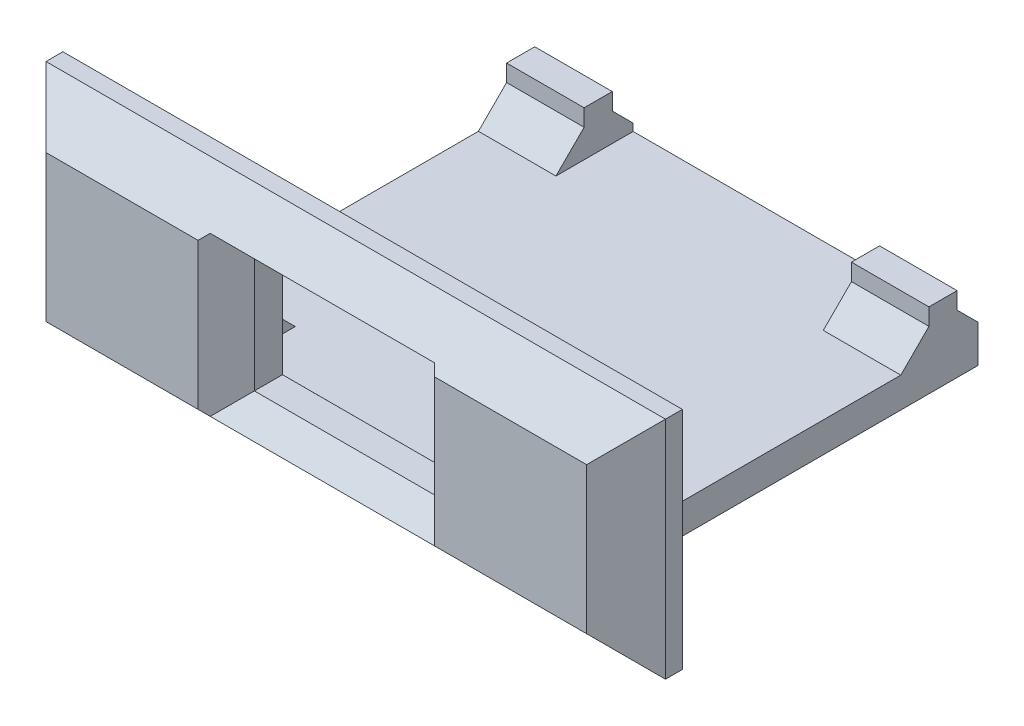
SolidWorks part; units mm, degrees
ref_plane "Спереди" through (0, 0, 0) normal (0, 0, 1) x (1, 0, 0)
ref_plane "Сверху" through (0, 0, 0) normal (0, 1, 0) x (1, 0, 0)
ref_plane "Справа" through (0, 0, 0) normal (1, 0, 0) x (0, 0, -1)
ref_plane "Плоскость4" through (0, 0, 727.8525) normal (0, 0, 1) x (1, 0, 0)
sketch "Эскиз1" plane through (0, 0, 727.8525) normal (0, 0, 1) x (1, 0, 0)
  line L0 (-220.0776, -84.8681) -> (-220.0776, -72.8681)
  line L1 (-208.0776, -72.8681) -> (-122.0776, -72.8681)
  line L2 (-220.0776, -84.8681) -> (-220.0776, -100.8681)
  line L3 (-208.0776, -112.8681) -> (-122.0776, -112.8681)
  line L4 (-110.0776, -84.8681) -> (-110.0776, -100.8681)
  line L5 (-208.0776, -72.8681) -> (-220.0776, -72.8681)
  line L6 (-122.0776, -72.8681) -> (-110.0776, -72.8681)
  line L7 (-110.0776, -84.8681) -> (-110.0776, -72.8681)
  line L8 (-208.0776, -112.8681) -> (-220.0776, -112.8681)
  line L9 (-220.0776, -100.8681) -> (-220.0776, -112.8681)
  line L10 (-110.0776, -100.8681) -> (-110.0776, -112.8681)
  line L11 (-122.0776, -112.8681) -> (-110.0776, -112.8681)
  point P6 (-110.0776, -112.8681)
  point P11 (-220.0776, -112.8681)
  point P14 (-220.0776, -72.8681)
  dimension "D1" = 110
  dimension "D2" = 40
extrude "Бобышка-Вытянуть1" add sketch "Эскиз1" along normal blind 10
sketch "Эскиз2" plane through (0, 0, 737.8525) normal (0, 0, 1) x (1, 0, 0)
  line L8 (-220.0776, -92.8681) -> (-110.0776, -92.8681) construction
  line L9 (-220.0776, -72.8681) -> (-220.0776, -112.8681) construction
  line L10 (-110.0776, -112.8681) -> (-110.0776, -72.8681) construction
  line L11 (-165.0776, -72.8681) -> (-165.0776, -112.8681) construction
  line L12 (-110.0776, -72.8681) -> (-220.0776, -72.8681) construction
  line L13 (-220.0776, -112.8681) -> (-110.0776, -112.8681) construction
  line L18 (-181.0776, -82.7081) -> (-181.0776, -103.0281)
  line L19 (-181.0776, -103.0281) -> (-149.0776, -103.0281)
  line L20 (-149.0776, -103.0281) -> (-149.0776, -82.7081)
  line L21 (-149.0776, -82.7081) -> (-181.0776, -82.7081)
  point P2 (-181.0776, -92.8681)
  point P16 (-165.0776, -82.7081)
  dimension "D1" = 20.32
  dimension "D2" = 20.32
  dimension "D3" = 32
extrude "Вырез-Вытянуть1" cut sketch "Эскиз2" against normal up to surface (10 mm away) up to face at (-165.0776, -92.8681, 727.8525)
ref_plane "Плоскость5" through (-165.0776, 0, 0) normal (1, 0, 0) x (0, 0, -1)
ref_plane "Плоскость6" through (0, -103.0281, 0) normal (0, 1, 0) x (1, 0, 0)
ref_plane "Плоскость7" through (0, 0, 727.8525) normal (0, 0, -1) x (-1, 0, 0)
fillet "Скругление1" radius 0.01 1 edges at (-165.0776, -103.0281, 727.8525)
fillet "Скругление2" radius 0.01 3 edges at (-149.0776, -92.8731, 727.8525) (-165.0776, -82.7081, 727.8525) (-181.0776, -92.8731, 727.8525)
sketch "Эскиз3" plane through (0, 0, 727.8525) normal (0, 0, -1) x (-1, 0, 0)
  line L0 (188.6126, -104.4966) -> (141.5426, -104.4966) construction
  line L1 (127.5776, -104.4966) -> (202.5776, -104.4966)
  line L2 (127.5776, -104.4966) -> (127.5776, -112.8681)
  line L3 (127.5776, -112.8681) -> (202.5776, -112.8681)
  line L4 (202.5776, -104.4966) -> (202.5776, -112.8681)
  line L5 (165.0776, -72.8681) -> (165.0776, -133.1733) construction
  point P6 (165.0776, -104.4966)
  point P9 (0, 0)
  point P12 (0, 0)
  dimension "D1" = 75
  dimension "D4" = 8.3715
extrude "Бобышка-Вытянуть2" add sketch "Эскиз3" along normal blind 70
sketch "Эскиз4" plane through (0, -104.4966, 0) normal (0, 1, 0) x (1, 0, 0)
  line L0 (-202.5776, -657.8525) -> (-202.5776, -727.8525) construction
  line L1 (-202.5776, -661.5629) -> (-188.8126, -661.5629)
  line L2 (-202.5776, -661.5629) -> (-202.5776, -666.5629)
  line L3 (-202.5776, -666.5629) -> (-188.8126, -666.5629)
  line L4 (-188.8126, -661.5629) -> (-188.8126, -666.5629)
  line L5 (-141.3426, -661.5629) -> (-127.5776, -661.5629)
  line L6 (-141.3426, -661.5629) -> (-141.3426, -666.5629)
  line L7 (-141.3426, -666.5629) -> (-127.5776, -666.5629)
  line L8 (-127.5776, -661.5629) -> (-127.5776, -666.5629)
  line L9 (-202.5776, -722.8525) -> (-188.8126, -722.8525)
  line L10 (-202.5776, -722.8525) -> (-202.5776, -727.8525)
  line L11 (-202.5776, -727.8525) -> (-188.8126, -727.8525)
  line L12 (-188.8126, -722.8525) -> (-188.8126, -727.8525)
  line L14 (-127.5776, -657.8525) -> (-127.5776, -727.8525) construction
  line L15 (-141.3426, -727.8525) -> (-127.5776, -727.8525)
  line L16 (-141.3426, -727.8525) -> (-141.3426, -722.8525)
  line L17 (-141.3426, -722.8525) -> (-127.5776, -722.8525)
  line L18 (-127.5776, -727.8525) -> (-127.5776, -722.8525)
  dimension "D1" = 5
  dimension "D2" = 5
  dimension "D3" = 5
  dimension "D4" = 5
  dimension "D5" = 13.765
  dimension "D6" = 13.765
  dimension "D7" = 13.765
  dimension "D8" = 13.765
extrude "Бобышка-Вытянуть3" add sketch "Эскиз4" along normal blind 8
chamfer "Фаска1" distance 5 angle 45 8 edges at (-195.6951, -96.4966, 727.8525) (-134.4601, -96.4966, 727.8525) (-134.4601, -104.4966, 666.5629) (-134.4601, -104.4966, 722.8525) (-134.4601, -104.4966, 661.5629) (-195.6951, -104.4966, 661.5629) (-195.6951, -104.4966, 722.8525) (-195.6951, -104.4966, 666.5629)
sketch "Эскиз5" plane through (0, -112.8681, 0) normal (0, -1, 0) x (1, 0, 0)
  line L0 (-22, 727.8525) -> (22, 727.8525) construction
  line L1 (-127.5776, 657.8525) -> (-202.5776, 657.8525)
  line L2 (-127.5776, 657.8525) -> (-127.5776, 727.8525)
  line L3 (-127.5776, 727.8525) -> (-202.5776, 727.8525)
  line L4 (-202.5776, 657.8525) -> (-202.5776, 727.8525)
  line L5 (14.8081, 727.8525) -> (-14.8081, 727.8525) construction
extrude "Вырез-Вытянуть2" cut sketch "Эскиз5" against normal blind 3
chamfer "Фаска2" distance 7 angle 45 4 edges at (-110.0776, -92.8681, 737.8525) (-165.0776, -72.8681, 737.8525) (-220.0776, -92.8681, 737.8525) (-165.0776, -112.8681, 737.8525)
chamfer "Фаска3" distance 5 angle 45 3 edges at (-181.0776, -92.8681, 737.8525) (-165.0776, -82.7081, 737.8525) (-149.0776, -92.8681, 737.8525)
chamfer "Фаска4" distance 5 angle 45 1 edges at (-165.0776, -103.0281, 737.8525)
